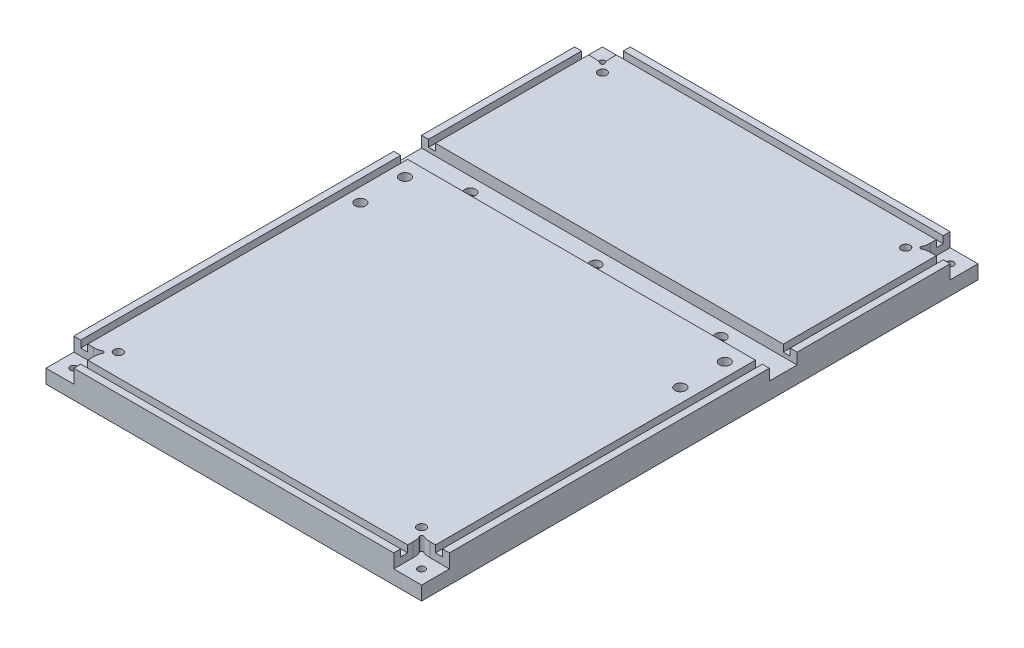
SolidWorks part; units mm, degrees
ref_plane "Front Plane" through (0, 0, 0) normal (0, 0, 1) x (1, 0, 0)
ref_plane "Top Plane" through (0, 0, 0) normal (0, 1, 0) x (1, 0, 0)
ref_plane "Right Plane" through (0, 0, 0) normal (1, 0, 0) x (0, 0, -1)
sketch "Base" plane through (0, 0, 0) normal (0, 1, 0) x (1, 0, 0)
  line L1 (-201.9764, 133.7508) -> (140.9236, 133.7508)
  line L2 (-201.9764, 133.7508) -> (-201.9764, -374.2492)
  line L3 (-201.9764, -374.2492) -> (140.9236, -374.2492)
  line L4 (140.9236, 133.7508) -> (140.9236, -374.2492)
  dimension "D1" = 342.9
  dimension "D2" = 508
extrude "Boss-Extrude1" add sketch "Base" along normal blind 25.4
sketch "Sketch2" plane through (0, 25.4, 0) normal (0, 1, 0) x (1, 0, 0)
  line L1 (172.6736, -31.3492) -> (-233.7264, -31.3492)
  line L2 (172.6736, -31.3492) -> (172.6736, -56.7492)
  line L3 (172.6736, -56.7492) -> (-233.7264, -56.7492)
  line L4 (-233.7264, -31.3492) -> (-233.7264, -56.7492)
  line L6 (140.9236, 133.7508) -> (-201.9764, 133.7508) construction
  line L9 (-30.5264, 133.7508) -> (-30.5264, -374.2492) construction
  line L10 (-201.9764, -374.2492) -> (140.9236, -374.2492) construction
  point P6 (-30.5264, -31.3492)
  dimension "D1" = 317.5
  dimension "D2" = 25.4
  dimension "D3" = 406.4
extrude "Cut-Extrude1" cut sketch "Sketch2" against normal blind 10.16
hole_wizard "CBORE for 3/8 Socket Head Cap Screw4" positions "3DSketch1" profile "Sketch3" counterbore size "3/8" standard "ANSI Inch" end condition up to next
sketch3d "3DSketch1"
  line L3 (-201.9764, 0, -133.7508) -> (-201.9764, 0, 374.2492) construction
  point P0 (83.7736, 0, 44.0492)
  point P2 (-30.5264, 0, 44.0492)
  point P4 (-144.8264, 0, 44.0492)
  dimension "D1" = 12.7
  dimension "D2" = 12.7
  dimension "D3" = 12.7
  dimension "D4" = 171.45
  dimension "D5" = 114.3
  dimension "D6" = 114.3
sketch "Sketch3" plane through (83.7736, 0, 44.0492) normal (1, 0, 0) x (0, 0, -1)
  line L0 (0, 0) -> (0, 15.24)
  line L1 (0, 15.24) -> (4.9022, 15.24)
  line L3 (4.9022, 15.24) -> (4.9022, 9.525)
  line L4 (4.9022, 9.525) -> (7.9375, 9.525)
  line L5 (7.9375, 9.525) -> (7.9375, 0)
  line L7 (7.9375, 0) -> (0, 0)
  line L11 (0, -6.35) -> (0, 107.95) construction
  dimension "Thru Hole Dia." = 9.8044
  dimension "Thru Hole Depth" = 15.24
  dimension "C'Bore Dia." = 15.875
  dimension "C'Bore Depth" = 9.525
hole_wizard "CBORE for 3/8 Socket Head Cap Screw3" positions "Sketch4" profile "Sketch6" counterbore size "3/8" standard "ANSI Inch" end condition up to next
sketch "Sketch4" plane through (0, 0, 0) normal (0, -1, 0) x (-1, 0, 0)
  line L0 (201.9764, -56.7492) -> (-140.9236, -56.7492) construction
  line L1 (-140.9236, -374.2492) -> (-140.9236, 133.7508) construction
  line L3 (201.9764, 133.7508) -> (201.9764, -374.2492) construction
  point P0 (-115.5236, -71.9892)
  point P2 (-115.5236, -112.6292)
  point P4 (176.5764, -71.9892)
  point P6 (176.5764, -112.6292)
  dimension "D1" = 15.24
  dimension "D2" = 25.4
  dimension "D3" = 25.4
  dimension "D4" = 40.64
  dimension "D5" = 15.24
  dimension "D6" = 25.4
  dimension "D7" = 40.64
  dimension "D8" = 25.4
sketch "Sketch6" plane through (115.5236, 0, 71.9892) normal (1, 0, 0) x (0, 0, -1)
  line L0 (0, 0) -> (0, 25.4)
  line L1 (0, 25.4) -> (4.9022, 25.4)
  line L3 (4.9022, 25.4) -> (4.9022, 15.24)
  line L4 (4.9022, 15.24) -> (7.9375, 15.24)
  line L5 (7.9375, 15.24) -> (7.9375, 0)
  line L7 (7.9375, 0) -> (0, 0)
  line L11 (0, -6.35) -> (0, 107.95) construction
  dimension "Thru Hole Dia." = 9.8044
  dimension "Thru Hole Depth" = 25.4
  dimension "C'Bore Dia." = 15.875
  dimension "C'Bore Depth" = 15.24
hole_wizard "CBORE for 1/4 Socket Head Cap Screw1" positions "3DSketch2" profile "Sketch9" counterbore size "1/4" standard "ANSI Inch" end condition up to next
sketch3d "3DSketch2"
  line L0 (140.9236, 0, -133.7508) -> (-201.9764, 0, -133.7508) construction
  line L1 (140.9236, 0, 374.2492) -> (140.9236, 0, -133.7508) construction
  line L2 (-201.9764, 0, -133.7508) -> (-201.9764, 0, 374.2492) construction
  line L3 (-201.9764, 0, 374.2492) -> (140.9236, 0, 374.2492) construction
  point P0 (128.2236, 0, 361.5492)
  point P2 (-189.2764, 0, 361.5492)
  point P4 (-189.2764, 0, -121.0508)
  point P6 (128.2236, 0, -121.0508)
  dimension "D1" = 12.7
  dimension "D2" = 12.7
  dimension "D3" = 12.7
  dimension "D4" = 12.7
  dimension "D5" = 12.7
  dimension "D6" = 12.7
  dimension "D7" = 12.7
  dimension "D8" = 12.7
sketch "Sketch9" plane through (128.2236, 0, 361.5492) normal (1, 0, 0) x (0, 0, -1)
  line L0 (0, 0) -> (0, 25.4)
  line L1 (0, 25.4) -> (3.2639, 25.4)
  line L3 (3.2639, 25.4) -> (3.2639, 6.35)
  line L4 (3.2639, 6.35) -> (5.5562, 6.35)
  line L5 (5.5562, 6.35) -> (5.5562, 0)
  line L7 (5.5562, 0) -> (0, 0)
  line L11 (0, -6.35) -> (0, 107.95) construction
  dimension "Thru Hole Dia." = 6.5278
  dimension "Thru Hole Depth" = 25.4
  dimension "C'Bore Dia." = 11.1125
  dimension "C'Bore Depth" = 6.35
sketch "Sketch8" plane through (0, 25.4, 0) normal (0, 1, 0) x (1, 0, 0)
  line L0 (116.3173, -347.4744) -> (115.5236, -348.8492) construction
  line L1 (140.9236, -374.2492) -> (115.5236, -374.2492)
  line L2 (140.9236, -374.2492) -> (140.9236, -348.8492)
  line L3 (140.9236, -348.8492) -> (123.1436, -348.8492)
  line L4 (115.5236, -374.2492) -> (115.5236, -356.4692)
  line L5 (-201.9764, -374.2492) -> (-176.5764, -374.2492)
  line L6 (-201.9764, -374.2492) -> (-201.9764, -348.8492)
  line L7 (-201.9764, -348.8492) -> (-184.1964, -348.8492)
  line L8 (-176.5764, -374.2492) -> (-176.5764, -356.4692)
  line L9 (-201.9764, 133.7508) -> (-176.5764, 133.7508)
  line L10 (-201.9764, 133.7508) -> (-201.9764, 108.3508)
  line L11 (-201.9764, 108.3508) -> (-184.1964, 108.3508)
  line L12 (-176.5764, 133.7508) -> (-176.5764, 115.9708)
  line L13 (140.9236, 133.7508) -> (115.5236, 133.7508)
  line L14 (140.9236, 133.7508) -> (140.9236, 108.3508)
  line L15 (140.9236, 108.3508) -> (123.1436, 108.3508)
  line L16 (115.5236, 133.7508) -> (115.5236, 115.9708)
  line L17 (115.5236, -348.8492) -> (123.1436, -348.8492) construction
  line L18 (115.5236, -356.4692) -> (115.5236, -348.8492) construction
  line L19 (115.5236, -348.8492) -> (114.1488, -349.6429) construction
  line L20 (115.5236, 108.3508) -> (116.3173, 106.976) construction
  line L21 (115.5236, 108.3508) -> (114.1488, 109.1446) construction
  line L22 (-176.5764, 108.3508) -> (-175.2016, 109.1446) construction
  line L23 (-176.5764, 108.3508) -> (-177.3702, 106.976) construction
  line L24 (-176.5764, -348.8492) -> (-175.2016, -349.6429) construction
  line L25 (-176.5764, -348.8492) -> (-177.3702, -347.4744) construction
  arc A0 (116.3173, -347.4744) -> (114.1488, -349.6429) centre (115.5236, -348.8492) ccw
  arc A1 (114.1488, 109.1446) -> (116.3173, 106.976) centre (115.5236, 108.3508) ccw
  arc A2 (-177.3702, 106.976) -> (-175.2016, 109.1446) centre (-176.5764, 108.3508) ccw
  arc A3 (-175.2016, -349.6429) -> (-177.3702, -347.4744) centre (-176.5764, -348.8492) ccw
  spline S0 degree 3 poles (123.1436, -348.8492) (120.8225, -348.8492) (118.3275, -348.6349) (116.3173, -347.4744) knots 0 0 0 0 1 1 1 1
  spline S1 degree 3 poles (115.5236, -356.4692) (115.5236, -353.9168) (115.3093, -351.6531) (114.1488, -349.6429) knots 0 0 0 0 1 1 1 1
  spline S2 degree 3 poles (123.1436, 108.3508) (120.8225, 108.3508) (118.3275, 108.1366) (116.3173, 106.976) knots 0 0 0 0 1 1 1 1
  spline S3 degree 3 poles (114.1488, 109.1446) (115.3093, 111.1547) (115.5236, 113.6497) (115.5236, 115.9708) knots 0 0 0 0 1 1 1 1
  spline S4 degree 3 poles (-176.5764, 115.9708) (-176.5764, 113.4184) (-176.3621, 111.1547) (-175.2016, 109.1446) knots 0 0 0 0 1 1 1 1
  spline S5 degree 3 poles (-177.3702, 106.976) (-179.3803, 108.1366) (-181.8753, 108.3508) (-184.1964, 108.3508) knots 0 0 0 0 1 1 1 1
  spline S6 degree 3 poles (-175.2016, -349.6429) (-176.7942, -352.4013) (-176.5764, -354.9687) (-176.5764, -356.4692) knots 0 0 0 0 1 1 1 1
  spline S7 degree 3 poles (-177.3702, -347.4744) (-180.1285, -349.0669) (-182.696, -348.8492) (-184.1964, -348.8492) knots 0 0 0 0 1 1 1 1
  point P23 (117.1111, -348.8492)
  point P27 (115.5236, -350.4367)
  dimension "D9" = 7.62
  dimension "D10" = 1.5875
  dimension "D15" = 60
  dimension "D16" = 1.5875
  dimension "D20" = 3.175
  dimension "D25" = 60
  dimension "D28" = 3.175
  dimension "D2" = 25.4
  dimension "D3" = 25.4
  dimension "D4" = 25.4
  dimension "D5" = 25.4
  dimension "D6" = 25.4
  dimension "D7" = 25.4
  dimension "D8" = 25.4
  dimension "D11" = 7.62
  dimension "D12" = 25.4
  dimension "D13" = 60
  dimension "D14" = 60
  dimension "D17" = 60
  dimension "D18" = 7.62
  dimension "D19" = 7.62
  dimension "D21" = 60
  dimension "D22" = 60
  dimension "D23" = 7.62
  dimension "D24" = 7.62
  dimension "D26" = 60
  dimension "D27" = 7.62
  dimension "D29" = 7.62
extrude "Cut-Extrude3" cut sketch "Sketch8" against normal blind 12.7
sketch "Sketch10" plane through (0, 25.4, 0) normal (0, 1, 0) x (1, 0, 0)
  line L1 (128.2236, 108.3508) -> (134.5736, 108.3508)
  line L2 (128.2236, 108.3508) -> (128.2236, -348.8492)
  line L3 (128.2236, -348.8492) -> (134.5736, -348.8492)
  line L4 (134.5736, 108.3508) -> (134.5736, -348.8492)
  line L5 (140.9236, -348.8492) -> (140.9236, -56.7492) construction
  line L8 (-201.9764, 108.3508) -> (-201.9764, -31.3492) construction
  line L9 (-195.6264, 108.3508) -> (-189.2764, 108.3508)
  line L10 (-195.6264, 108.3508) -> (-195.6264, -348.8492)
  line L11 (-195.6264, -348.8492) -> (-189.2764, -348.8492)
  line L12 (-189.2764, 108.3508) -> (-189.2764, -348.8492)
  line L13 (-184.1964, -348.8492) -> (-201.9764, -348.8492) construction
  line L14 (-201.9764, 108.3508) -> (-184.1964, 108.3508) construction
  line L15 (123.1436, 108.3508) -> (140.9236, 108.3508) construction
  line L16 (140.9236, -348.8492) -> (123.1436, -348.8492) construction
  line L17 (-176.5764, 115.9708) -> (-176.5764, 133.7508) construction
  line L18 (-176.5764, 127.4008) -> (115.5236, 127.4008)
  line L19 (-176.5764, 127.4008) -> (-176.5764, 121.0508)
  line L20 (-176.5764, 121.0508) -> (115.5236, 121.0508)
  line L21 (115.5236, 127.4008) -> (115.5236, 121.0508)
  line L22 (115.5236, 133.7508) -> (115.5236, 115.9708) construction
  line L23 (115.5236, 133.7508) -> (-176.5764, 133.7508) construction
  line L24 (-176.5764, -374.2492) -> (-176.5764, -356.4692) construction
  line L25 (-176.5764, -361.5492) -> (115.5236, -361.5492)
  line L26 (-176.5764, -361.5492) -> (-176.5764, -367.8992)
  line L27 (-176.5764, -367.8992) -> (115.5236, -367.8992)
  line L28 (115.5236, -361.5492) -> (115.5236, -367.8992)
  line L29 (115.5236, -356.4692) -> (115.5236, -374.2492) construction
  line L30 (-176.5764, -374.2492) -> (115.5236, -374.2492) construction
  dimension "D1" = 6.35
  dimension "D2" = 6.35
  dimension "D3" = 6.35
  dimension "D4" = 6.35
  dimension "D5" = 6.35
  dimension "D6" = 6.35
  dimension "D7" = 6.35
  dimension "D8" = 6.35
extrude "Cut-Extrude4" cut sketch "Sketch10" against normal blind 6.35
hole_wizard "3/8-16 Tapped Hole2" positions "Sketch17" profile "Sketch18" tap size "3/8-16" standard "ANSI Inch" end condition up to next
sketch "Sketch17" plane through (0, 0, 0) normal (0, -1, 0) x (-1, 0, 0)
  line L0 (-140.9236, 133.7508) -> (201.9764, 133.7508) construction
  line L1 (-140.9236, -374.2492) -> (-140.9236, 133.7508) construction
  line L2 (201.9764, 133.7508) -> (201.9764, -374.2492) construction
  line L3 (201.9764, -374.2492) -> (-140.9236, -374.2492) construction
  point P0 (-107.9036, -341.2292)
  point P2 (168.9564, -341.2292)
  point P4 (168.9564, 100.7308)
  point P6 (-107.9036, 100.7308)
  dimension "D1" = 33.02
  dimension "D2" = 33.02
  dimension "D3" = 33.02
  dimension "D4" = 33.02
  dimension "D5" = 33.02
  dimension "D6" = 33.02
  dimension "D7" = 33.02
  dimension "D8" = 33.02
sketch "Sketch18" plane through (107.9036, 0, 341.2292) normal (1, 0, 0) x (0, 0, -1)
  line L0 (0, 0) -> (0, 25.4)
  line L1 (0, 25.4) -> (3.9687, 25.4)
  line L2 (3.9687, 25.4) -> (3.9687, 0)
  line L5 (3.9687, 0) -> (0, 0)
  line L11 (0, -6.35) -> (0, 107.95) construction
  dimension "Thru Tap Drill Dia." = 7.9375
  dimension "Thru Tap Drill Depth" = 25.4
cosmetic thread "Hole Thread5" parameters "D2"=9.525
cosmetic thread "Hole Thread6" parameters "D2"=9.525
cosmetic thread "Hole Thread7" parameters "D2"=9.525
cosmetic thread "Hole Thread8" parameters "D2"=9.525
sketch "Sketch19" plane through (0, 0, 0) normal (0, -1, 0) x (1, 0, 0)
  circle A0 centre (-168.9564, -100.7308) radius 9.525
  circle A1 centre (-168.9564, 341.2292) radius 9.525
  circle A2 centre (107.9036, 341.2292) radius 9.525
  circle A3 centre (108.2173, -100.7308) radius 9.525
  dimension "D1" = 19.05
  dimension "D2" = 19.05
  dimension "D3" = 19.05
  dimension "D4" = 19.05
extrude "Cut-Extrude5" cut sketch "Sketch19" against normal blind 1.27
ref_plane "Plane1" through (0, 0, 120.2492) normal (0, 0, 1) x (1, 0, 0)
